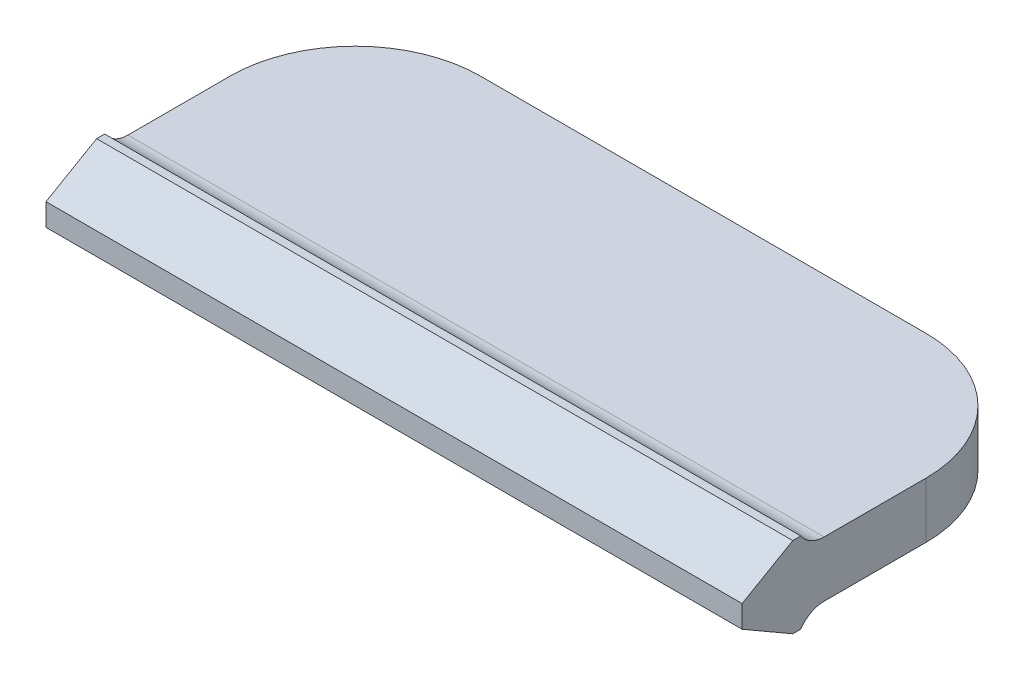
SolidWorks part; units mm, degrees
ref_plane "Top" through (0, 0, 0) normal (0, 0, 1) x (1, 0, 0)
ref_plane "Front" through (0, 0, 0) normal (0, 1, 0) x (1, 0, 0)
ref_plane "Right" through (0, 0, 0) normal (1, 0, 0) x (0, 0, -1)
sketch "Connection Sketch" plane through (0, 0, 0) normal (1, 0, 0) x (0, 0, -1)
  line L0 (0, 1.45) -> (0, 1)
  line L1 (0, -1.6) -> (-0.3287, -1.6) construction
  line L2 (-0.3287, -1.6) -> (-3.1, 0) construction
  line L5 (-3.1, 0) -> (-0.3287, 1.6) construction
  line L6 (-0.3287, 1.6) -> (0, 1.6) construction
  line L7 (-3.1, 0) -> (0, 0) construction
  line L8 (-3.1, 0) -> (-3.1, 1.6) construction
  line L11 (0, 1.45) -> (-0.2885, 1.45)
  line L12 (-0.2885, 1.45) -> (-2.1072, 0.4)
  line L13 (-2.1072, 0.4) -> (-2.1072, -0.4)
  line L14 (-2.1072, -0.4) -> (-0.2885, -1.45)
  line L15 (-0.2885, -1.45) -> (0, -1.45)
  line L16 (0, 1.6) -> (0, 1.45) construction
  line L17 (0, -1.45) -> (0, -1.6) construction
  line L18 (0, -1) -> (9, -1)
  line L19 (9, -1) -> (9, 1)
  line L20 (9, 1) -> (0, 1)
  line L21 (0, -1) -> (0, -1.45)
  line L22 (0, -1) -> (0, 1) construction
  point P11 (0, 0)
  point P18 (0, 0)
  point P19 (0, 0)
  dimension "D1" = 60
  dimension "D2" = 3.2
  dimension "D7" = 0.8
  dimension "D8" = 3.1
  dimension "D4" = 0.15
  dimension "D3" = 0.15
  dimension "D6" = 0.15
  dimension "D5" = 0.15
  dimension "D9" = 0.3287
  dimension "D10" = 2
  dimension "D11" = 9
extrude "Connection Extrude" add sketch "Connection Sketch" along normal blind 25 separate body
fillet "Top Fillets" radius 4.5 2 edges at (25, 0, -9) (0, 0, -9)
fillet "Connection Fillets" radius 1 2 edges at (12.5, 1, 0) (12.5, -1, 0)
equation "\"Handle Thickness\"= 2"
equation "\"Connection Chamfer Angle\"= 60deg"
equation "\"Connecion Clearance\"= 0.15mm"
equation "\"D1@Connection Sketch\"=\"Connection Chamfer Angle\""
equation "\"D4@Connection Sketch\"=\"Connecion Clearance\""
equation "\"D3@Connection Sketch\"=\"Connecion Clearance\""
equation "\"D6@Connection Sketch\"=\"Connecion Clearance\""
equation "\"D5@Connection Sketch\"=\"Connecion Clearance\""
equation "\"D10@Connection Sketch\"=\"Handle Thickness\""
